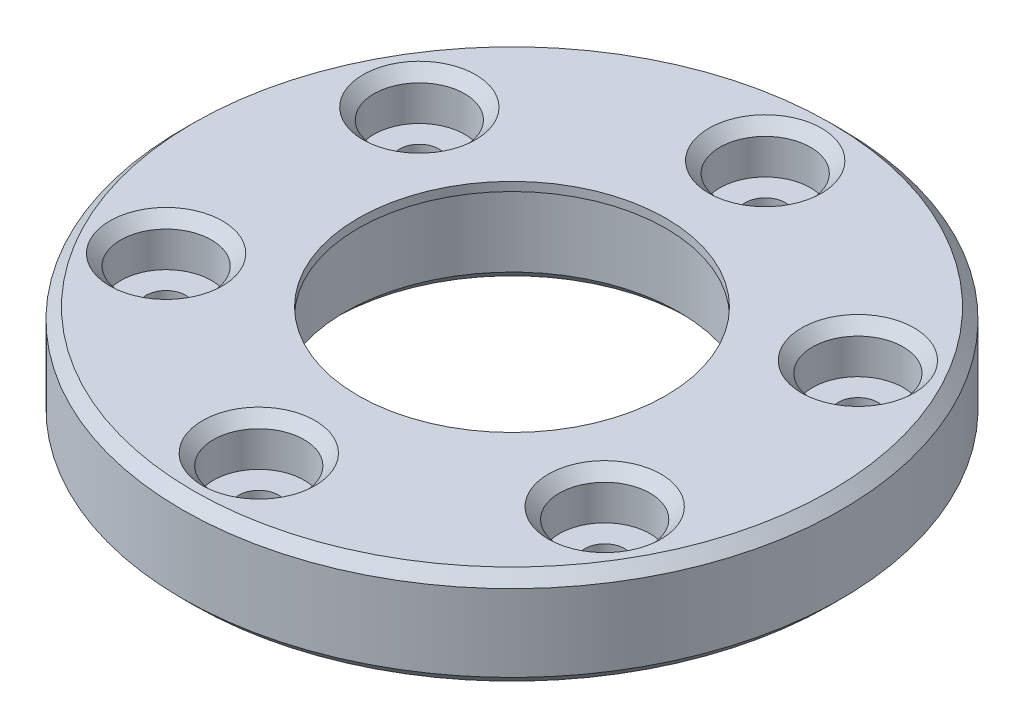
SolidWorks part; units mm, degrees
ref_plane "前视基准面" through (0, 0, 0) normal (0, 0, 1) x (1, 0, 0)
ref_plane "上视基准面" through (0, 0, 0) normal (0, 1, 0) x (1, 0, 0)
ref_plane "右视基准面" through (0, 0, 0) normal (1, 0, 0) x (0, 0, -1)
other "Configuration Table"
sketch "草图1" plane through (0, 0, 0) normal (0, 1, 0) x (1, 0, 0)
  circle A0 centre (0, 0) radius 7
  circle A1 centre (0, 0) radius 15
  circle A2 centre (0, 0) radius 11.525 construction
  circle A3 centre (0, 11.525) radius 2.065
  circle A4 centre (9.9809, 5.7625) radius 2.065
  circle A5 centre (9.9809, -5.7625) radius 2.065
  circle A6 centre (0, -11.525) radius 2.065
  circle A7 centre (-9.9809, -5.7625) radius 2.065
  circle A8 centre (-9.9809, 5.7625) radius 2.065
  point P19 (0, 0)
  dimension "D1" = 14
  dimension "D2" = 30
  dimension "D3" = 23.05
  dimension "D4" = 4.13
  dimension "D5" = 6
extrude "凸台-拉伸1" add sketch "草图1" along normal blind 2.1
sketch "草图2" plane through (0, 0, 0) normal (0, -1, 0) x (-1, 0, 0)
  circle A0 centre (0, 0) radius 7 construction
  circle A1 centre (0, 0) radius 15 construction
  circle A2 centre (0, 0) radius 7
  circle A3 centre (0, 0) radius 15
  circle A4 centre (0, 11.53) radius 0.9
  circle A6 centre (0, 0) radius 11.53 construction
  circle A7 centre (9.9853, 5.765) radius 0.9
  circle A8 centre (9.9853, -5.765) radius 0.9
  circle A9 centre (0, -11.53) radius 0.9
  circle A10 centre (-9.9853, -5.765) radius 0.9
  circle A11 centre (-9.9853, 5.765) radius 0.9
  point P21 (0, 0)
  dimension "D1" = 1.8
  dimension "D2" = 23.06
  dimension "D3" = 6
extrude "凸台-拉伸2" add sketch "草图2" along normal blind 2.4
sketch "草图3" plane through (0, -2.4, 0) normal (0, -1, 0) x (-1, 0, 0)
  circle A0 centre (0, 0) radius 7.6
  dimension "D1" = 15.2
extrude "切除-拉伸1" cut sketch "草图3" against normal blind 4.1
chamfer "倒角1" distance 0.5 angle 45 15 edges at (0, -2.4, -15) (-9.9809, 2.1, -3.6975) (0, 2.1, 13.59) (9.9809, 2.1, -3.6975) (0, 2.1, 15) (0, 2.1, -9.46) (9.9809, 2.1, 7.8275) (-9.9809, 2.1, 7.8275) (9.9853, -2.4, -6.665) (0, -2.4, 10.63) (-9.9853, -2.4, -6.665) (0, -2.4, -12.43) (-9.9853, -2.4, 4.865) (9.9853, -2.4, 4.865) (0, -2.4, -7.6)
chamfer "倒角2" distance 0.3 angle 45 1 edges at (0, 1.7, -7.6)
